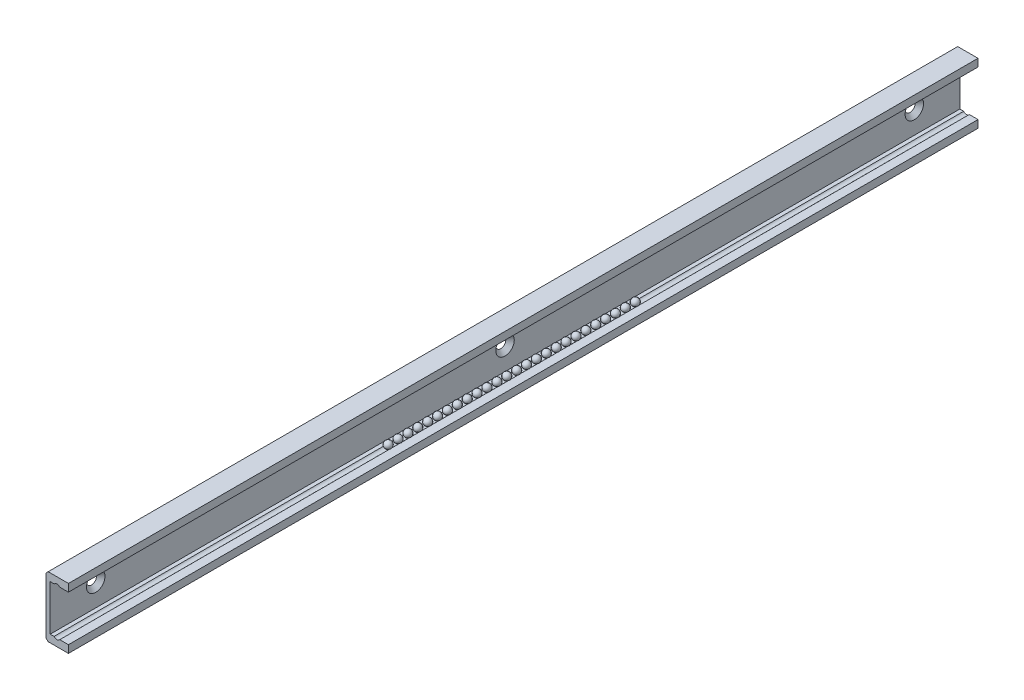
SolidWorks part; units mm, degrees
ref_plane "Front" through (0, 0, 0) normal (0, 0, 1) x (1, 0, 0)
ref_plane "Top" through (0, 0, 0) normal (0, 1, 0) x (1, 0, 0)
ref_plane "Right" through (0, 0, 0) normal (1, 0, 0) x (0, 0, -1)
ref_plane "Plane1" through (0, 0, 0) normal (0, 0, 1) x (1, 0, 0)
sketch "Sketch1" plane through (0, 0, 0) normal (0, 0, 1) x (1, 0, 0)
  line L0 (-7.4, 0.7071) -> (-6.6929, 0)
  line L1 (-6.6929, 0) -> (0, 0)
  line L2 (0, 0) -> (0, 2.5)
  line L3 (0, 2.5) -> (-2.8633, 2.5)
  line L4 (-4.7367, 2.5) -> (-6, 2.5)
  line L5 (-6, 2.5) -> (-6, 17.5)
  line L6 (-6, 17.5) -> (-4.7367, 17.5)
  line L7 (-2.8633, 17.5) -> (0, 17.5)
  line L8 (0, 17.5) -> (0, 20)
  line L9 (0, 20) -> (-6.6929, 20)
  line L10 (-6.6929, 20) -> (-7.4, 19.2929)
  line L11 (-7.4, 19.2929) -> (-7.4, 0.7071)
  arc A0 (-2.8633, 2.5) -> (-4.7367, 2.5) centre (-3.8, 3.25) cw
  arc A1 (-4.7367, 17.5) -> (-2.8633, 17.5) centre (-3.8, 16.75) cw
extrude "Boss-Extrude1" add sketch "Sketch1" along normal blind 300
ref_plane "Plane2" through (0, 0, 15) normal (0, 0, 1) x (1, 0, 0)
sketch "Sketch2" plane through (0, 0, 15) normal (0, 0, 1) x (1, 0, 0)
  line L0 (-7.4, 10) -> (-7.4, 11.65)
  line L1 (-7.4, 11.65) -> (-6, 13.05)
  line L2 (-6, 13.05) -> (-6, 10)
  line L3 (-6, 10) -> (-7.4, 10)
  line L4 (-6, 10) -> (-7.4, 10) construction
revolve "Cut-Revolve1" cut sketch "Sketch2" angle 360 about L4 reverse direction yes
ref_plane "Plane3" through (0, 0, 285) normal (0, 0, 1) x (1, 0, 0)
sketch "Sketch3" plane through (0, 0, 285) normal (0, 0, 1) x (1, 0, 0)
  line L0 (-7.4, 10) -> (-7.4, 11.65)
  line L1 (-7.4, 11.65) -> (-6, 13.05)
  line L2 (-6, 13.05) -> (-6, 10)
  line L3 (-6, 10) -> (-7.4, 10)
  line L4 (-6, 10) -> (-7.4, 10) construction
revolve "Cut-Revolve2" cut sketch "Sketch3" angle 360 about L4 reverse direction yes
ref_plane "Plane4" through (0, 0, 150) normal (0, 0, 1) x (1, 0, 0)
sketch "Sketch4" plane through (0, 0, 150) normal (0, 0, 1) x (1, 0, 0)
  line L0 (-7.4, 10) -> (-7.4, 11.65)
  line L1 (-7.4, 11.65) -> (-6, 13.05)
  line L2 (-6, 13.05) -> (-6, 10)
  line L3 (-6, 10) -> (-7.4, 10)
  line L4 (-6, 10) -> (-7.4, 10) construction
revolve "Cut-Revolve3" cut sketch "Sketch4" angle 360 about L4 reverse direction yes
ref_plane "Plane5" through (0, 3.15, 0) normal (0, 1, 0) x (1, 0, 0)
sketch "Sketch5" plane through (0, 3.15, 0) normal (0, 1, 0) x (1, 0, 0)
  line L0 (-3.8, -110.45) -> (-3.8, -108.05)
  line L1 (-3.8, -110.45) -> (-3.8, -108.05) construction
  arc A0 (-3.8, -108.05) -> (-3.8, -110.45) centre (-3.8, -109.25) cw
revolve "Revolve1" add sketch "Sketch5" angle 360 about L1 reverse direction yes
ref_plane "Plane6" through (0, 3.15, 0) normal (0, 1, 0) x (1, 0, 0)
sketch "Sketch6" plane through (0, 3.15, 0) normal (0, 1, 0) x (1, 0, 0)
  line L0 (-3.8, -113.71) -> (-3.8, -111.31)
  line L1 (-3.8, -113.71) -> (-3.8, -111.31) construction
  arc A0 (-3.8, -111.31) -> (-3.8, -113.71) centre (-3.8, -112.51) cw
revolve "Revolve2" add sketch "Sketch6" angle 360 about L1 reverse direction yes
ref_plane "Plane7" through (0, 3.15, 0) normal (0, 1, 0) x (1, 0, 0)
sketch "Sketch7" plane through (0, 3.15, 0) normal (0, 1, 0) x (1, 0, 0)
  line L0 (-3.8, -116.97) -> (-3.8, -114.57)
  line L1 (-3.8, -116.97) -> (-3.8, -114.57) construction
  arc A0 (-3.8, -114.57) -> (-3.8, -116.97) centre (-3.8, -115.77) cw
revolve "Revolve3" add sketch "Sketch7" angle 360 about L1 reverse direction yes
ref_plane "Plane8" through (0, 3.15, 0) normal (0, 1, 0) x (1, 0, 0)
sketch "Sketch8" plane through (0, 3.15, 0) normal (0, 1, 0) x (1, 0, 0)
  line L0 (-3.8, -120.23) -> (-3.8, -117.83)
  line L1 (-3.8, -120.23) -> (-3.8, -117.83) construction
  arc A0 (-3.8, -117.83) -> (-3.8, -120.23) centre (-3.8, -119.03) cw
revolve "Revolve4" add sketch "Sketch8" angle 360 about L1 reverse direction yes
ref_plane "Plane9" through (0, 3.15, 0) normal (0, 1, 0) x (1, 0, 0)
sketch "Sketch9" plane through (0, 3.15, 0) normal (0, 1, 0) x (1, 0, 0)
  line L0 (-3.8, -123.49) -> (-3.8, -121.09)
  line L1 (-3.8, -123.49) -> (-3.8, -121.09) construction
  arc A0 (-3.8, -121.09) -> (-3.8, -123.49) centre (-3.8, -122.29) cw
revolve "Revolve5" add sketch "Sketch9" angle 360 about L1 reverse direction yes
ref_plane "Plane10" through (0, 3.15, 0) normal (0, 1, 0) x (1, 0, 0)
sketch "Sketch10" plane through (0, 3.15, 0) normal (0, 1, 0) x (1, 0, 0)
  line L0 (-3.8, -126.75) -> (-3.8, -124.35)
  line L1 (-3.8, -126.75) -> (-3.8, -124.35) construction
  arc A0 (-3.8, -124.35) -> (-3.8, -126.75) centre (-3.8, -125.55) cw
revolve "Revolve6" add sketch "Sketch10" angle 360 about L1 reverse direction yes
ref_plane "Plane11" through (0, 3.15, 0) normal (0, 1, 0) x (1, 0, 0)
sketch "Sketch11" plane through (0, 3.15, 0) normal (0, 1, 0) x (1, 0, 0)
  line L0 (-3.8, -130.01) -> (-3.8, -127.61)
  line L1 (-3.8, -130.01) -> (-3.8, -127.61) construction
  arc A0 (-3.8, -127.61) -> (-3.8, -130.01) centre (-3.8, -128.81) cw
revolve "Revolve7" add sketch "Sketch11" angle 360 about L1 reverse direction yes
ref_plane "Plane12" through (0, 3.15, 0) normal (0, 1, 0) x (1, 0, 0)
sketch "Sketch12" plane through (0, 3.15, 0) normal (0, 1, 0) x (1, 0, 0)
  line L0 (-3.8, -133.27) -> (-3.8, -130.87)
  line L1 (-3.8, -133.27) -> (-3.8, -130.87) construction
  arc A0 (-3.8, -130.87) -> (-3.8, -133.27) centre (-3.8, -132.07) cw
revolve "Revolve8" add sketch "Sketch12" angle 360 about L1 reverse direction yes
ref_plane "Plane13" through (0, 3.15, 0) normal (0, 1, 0) x (1, 0, 0)
sketch "Sketch13" plane through (0, 3.15, 0) normal (0, 1, 0) x (1, 0, 0)
  line L0 (-3.8, -136.53) -> (-3.8, -134.13)
  line L1 (-3.8, -136.53) -> (-3.8, -134.13) construction
  arc A0 (-3.8, -134.13) -> (-3.8, -136.53) centre (-3.8, -135.33) cw
revolve "Revolve9" add sketch "Sketch13" angle 360 about L1 reverse direction yes
ref_plane "Plane14" through (0, 3.15, 0) normal (0, 1, 0) x (1, 0, 0)
sketch "Sketch14" plane through (0, 3.15, 0) normal (0, 1, 0) x (1, 0, 0)
  line L0 (-3.8, -139.79) -> (-3.8, -137.39)
  line L1 (-3.8, -139.79) -> (-3.8, -137.39) construction
  arc A0 (-3.8, -137.39) -> (-3.8, -139.79) centre (-3.8, -138.59) cw
revolve "Revolve10" add sketch "Sketch14" angle 360 about L1 reverse direction yes
ref_plane "Plane15" through (0, 3.15, 0) normal (0, 1, 0) x (1, 0, 0)
sketch "Sketch15" plane through (0, 3.15, 0) normal (0, 1, 0) x (1, 0, 0)
  line L0 (-3.8, -143.05) -> (-3.8, -140.65)
  line L1 (-3.8, -143.05) -> (-3.8, -140.65) construction
  arc A0 (-3.8, -140.65) -> (-3.8, -143.05) centre (-3.8, -141.85) cw
revolve "Revolve11" add sketch "Sketch15" angle 360 about L1 reverse direction yes
ref_plane "Plane16" through (0, 3.15, 0) normal (0, 1, 0) x (1, 0, 0)
sketch "Sketch16" plane through (0, 3.15, 0) normal (0, 1, 0) x (1, 0, 0)
  line L0 (-3.8, -146.31) -> (-3.8, -143.91)
  line L1 (-3.8, -146.31) -> (-3.8, -143.91) construction
  arc A0 (-3.8, -143.91) -> (-3.8, -146.31) centre (-3.8, -145.11) cw
revolve "Revolve12" add sketch "Sketch16" angle 360 about L1 reverse direction yes
ref_plane "Plane17" through (0, 3.15, 0) normal (0, 1, 0) x (1, 0, 0)
sketch "Sketch17" plane through (0, 3.15, 0) normal (0, 1, 0) x (1, 0, 0)
  line L0 (-3.8, -149.57) -> (-3.8, -147.17)
  line L1 (-3.8, -149.57) -> (-3.8, -147.17) construction
  arc A0 (-3.8, -147.17) -> (-3.8, -149.57) centre (-3.8, -148.37) cw
revolve "Revolve13" add sketch "Sketch17" angle 360 about L1 reverse direction yes
ref_plane "Plane18" through (0, 3.15, 0) normal (0, 1, 0) x (1, 0, 0)
sketch "Sketch18" plane through (0, 3.15, 0) normal (0, 1, 0) x (1, 0, 0)
  line L0 (-3.8, -152.83) -> (-3.8, -150.43)
  line L1 (-3.8, -152.83) -> (-3.8, -150.43) construction
  arc A0 (-3.8, -150.43) -> (-3.8, -152.83) centre (-3.8, -151.63) cw
revolve "Revolve14" add sketch "Sketch18" angle 360 about L1 reverse direction yes
ref_plane "Plane19" through (0, 3.15, 0) normal (0, 1, 0) x (1, 0, 0)
sketch "Sketch19" plane through (0, 3.15, 0) normal (0, 1, 0) x (1, 0, 0)
  line L0 (-3.8, -156.09) -> (-3.8, -153.69)
  line L1 (-3.8, -156.09) -> (-3.8, -153.69) construction
  arc A0 (-3.8, -153.69) -> (-3.8, -156.09) centre (-3.8, -154.89) cw
revolve "Revolve15" add sketch "Sketch19" angle 360 about L1 reverse direction yes
ref_plane "Plane20" through (0, 3.15, 0) normal (0, 1, 0) x (1, 0, 0)
sketch "Sketch20" plane through (0, 3.15, 0) normal (0, 1, 0) x (1, 0, 0)
  line L0 (-3.8, -159.35) -> (-3.8, -156.95)
  line L1 (-3.8, -159.35) -> (-3.8, -156.95) construction
  arc A0 (-3.8, -156.95) -> (-3.8, -159.35) centre (-3.8, -158.15) cw
revolve "Revolve16" add sketch "Sketch20" angle 360 about L1 reverse direction yes
ref_plane "Plane21" through (0, 3.15, 0) normal (0, 1, 0) x (1, 0, 0)
sketch "Sketch21" plane through (0, 3.15, 0) normal (0, 1, 0) x (1, 0, 0)
  line L0 (-3.8, -162.61) -> (-3.8, -160.21)
  line L1 (-3.8, -162.61) -> (-3.8, -160.21) construction
  arc A0 (-3.8, -160.21) -> (-3.8, -162.61) centre (-3.8, -161.41) cw
revolve "Revolve17" add sketch "Sketch21" angle 360 about L1 reverse direction yes
ref_plane "Plane22" through (0, 3.15, 0) normal (0, 1, 0) x (1, 0, 0)
sketch "Sketch22" plane through (0, 3.15, 0) normal (0, 1, 0) x (1, 0, 0)
  line L0 (-3.8, -165.87) -> (-3.8, -163.47)
  line L1 (-3.8, -165.87) -> (-3.8, -163.47) construction
  arc A0 (-3.8, -163.47) -> (-3.8, -165.87) centre (-3.8, -164.67) cw
revolve "Revolve18" add sketch "Sketch22" angle 360 about L1 reverse direction yes
ref_plane "Plane23" through (0, 3.15, 0) normal (0, 1, 0) x (1, 0, 0)
sketch "Sketch23" plane through (0, 3.15, 0) normal (0, 1, 0) x (1, 0, 0)
  line L0 (-3.8, -169.13) -> (-3.8, -166.73)
  line L1 (-3.8, -169.13) -> (-3.8, -166.73) construction
  arc A0 (-3.8, -166.73) -> (-3.8, -169.13) centre (-3.8, -167.93) cw
revolve "Revolve19" add sketch "Sketch23" angle 360 about L1 reverse direction yes
ref_plane "Plane24" through (0, 3.15, 0) normal (0, 1, 0) x (1, 0, 0)
sketch "Sketch24" plane through (0, 3.15, 0) normal (0, 1, 0) x (1, 0, 0)
  line L0 (-3.8, -172.39) -> (-3.8, -169.99)
  line L1 (-3.8, -172.39) -> (-3.8, -169.99) construction
  arc A0 (-3.8, -169.99) -> (-3.8, -172.39) centre (-3.8, -171.19) cw
revolve "Revolve20" add sketch "Sketch24" angle 360 about L1 reverse direction yes
ref_plane "Plane25" through (0, 3.15, 0) normal (0, 1, 0) x (1, 0, 0)
sketch "Sketch25" plane through (0, 3.15, 0) normal (0, 1, 0) x (1, 0, 0)
  line L0 (-3.8, -175.65) -> (-3.8, -173.25)
  line L1 (-3.8, -175.65) -> (-3.8, -173.25) construction
  arc A0 (-3.8, -173.25) -> (-3.8, -175.65) centre (-3.8, -174.45) cw
revolve "Revolve21" add sketch "Sketch25" angle 360 about L1 reverse direction yes
ref_plane "Plane26" through (0, 3.15, 0) normal (0, 1, 0) x (1, 0, 0)
sketch "Sketch26" plane through (0, 3.15, 0) normal (0, 1, 0) x (1, 0, 0)
  line L0 (-3.8, -178.91) -> (-3.8, -176.51)
  line L1 (-3.8, -178.91) -> (-3.8, -176.51) construction
  arc A0 (-3.8, -176.51) -> (-3.8, -178.91) centre (-3.8, -177.71) cw
revolve "Revolve22" add sketch "Sketch26" angle 360 about L1 reverse direction yes
ref_plane "Plane27" through (0, 3.15, 0) normal (0, 1, 0) x (1, 0, 0)
sketch "Sketch27" plane through (0, 3.15, 0) normal (0, 1, 0) x (1, 0, 0)
  line L0 (-3.8, -182.17) -> (-3.8, -179.77)
  line L1 (-3.8, -182.17) -> (-3.8, -179.77) construction
  arc A0 (-3.8, -179.77) -> (-3.8, -182.17) centre (-3.8, -180.97) cw
revolve "Revolve23" add sketch "Sketch27" angle 360 about L1 reverse direction yes
ref_plane "Plane28" through (0, 3.15, 0) normal (0, 1, 0) x (1, 0, 0)
sketch "Sketch28" plane through (0, 3.15, 0) normal (0, 1, 0) x (1, 0, 0)
  line L0 (-3.8, -185.43) -> (-3.8, -183.03)
  line L1 (-3.8, -185.43) -> (-3.8, -183.03) construction
  arc A0 (-3.8, -183.03) -> (-3.8, -185.43) centre (-3.8, -184.23) cw
revolve "Revolve24" add sketch "Sketch28" angle 360 about L1 reverse direction yes
ref_plane "Plane29" through (0, 3.15, 0) normal (0, 1, 0) x (1, 0, 0)
sketch "Sketch29" plane through (0, 3.15, 0) normal (0, 1, 0) x (1, 0, 0)
  line L0 (-3.8, -188.69) -> (-3.8, -186.29)
  line L1 (-3.8, -188.69) -> (-3.8, -186.29) construction
  arc A0 (-3.8, -186.29) -> (-3.8, -188.69) centre (-3.8, -187.49) cw
revolve "Revolve25" add sketch "Sketch29" angle 360 about L1 reverse direction yes
ref_plane "Plane30" through (0, 3.15, 0) normal (0, 1, 0) x (1, 0, 0)
sketch "Sketch30" plane through (0, 3.15, 0) normal (0, 1, 0) x (1, 0, 0)
  line L0 (-3.8, -191.95) -> (-3.8, -189.55)
  line L1 (-3.8, -191.95) -> (-3.8, -189.55) construction
  arc A0 (-3.8, -189.55) -> (-3.8, -191.95) centre (-3.8, -190.75) cw
revolve "Revolve26" add sketch "Sketch30" angle 360 about L1 reverse direction yes
ref_plane "Plane31" through (0, 16.85, 0) normal (0, 1, 0) x (1, 0, 0)
sketch "Sketch31" plane through (0, 16.85, 0) normal (0, 1, 0) x (1, 0, 0)
  line L0 (-3.8, -110.45) -> (-3.8, -108.05)
  line L1 (-3.8, -110.45) -> (-3.8, -108.05) construction
  arc A0 (-3.8, -108.05) -> (-3.8, -110.45) centre (-3.8, -109.25) cw
revolve "Revolve27" add sketch "Sketch31" angle 360 about L1 reverse direction yes
ref_plane "Plane32" through (0, 16.85, 0) normal (0, 1, 0) x (1, 0, 0)
sketch "Sketch32" plane through (0, 16.85, 0) normal (0, 1, 0) x (1, 0, 0)
  line L0 (-3.8, -113.71) -> (-3.8, -111.31)
  line L1 (-3.8, -113.71) -> (-3.8, -111.31) construction
  arc A0 (-3.8, -111.31) -> (-3.8, -113.71) centre (-3.8, -112.51) cw
revolve "Revolve28" add sketch "Sketch32" angle 360 about L1 reverse direction yes
ref_plane "Plane33" through (0, 16.85, 0) normal (0, 1, 0) x (1, 0, 0)
sketch "Sketch33" plane through (0, 16.85, 0) normal (0, 1, 0) x (1, 0, 0)
  line L0 (-3.8, -116.97) -> (-3.8, -114.57)
  line L1 (-3.8, -116.97) -> (-3.8, -114.57) construction
  arc A0 (-3.8, -114.57) -> (-3.8, -116.97) centre (-3.8, -115.77) cw
revolve "Revolve29" add sketch "Sketch33" angle 360 about L1 reverse direction yes
ref_plane "Plane34" through (0, 16.85, 0) normal (0, 1, 0) x (1, 0, 0)
sketch "Sketch34" plane through (0, 16.85, 0) normal (0, 1, 0) x (1, 0, 0)
  line L0 (-3.8, -120.23) -> (-3.8, -117.83)
  line L1 (-3.8, -120.23) -> (-3.8, -117.83) construction
  arc A0 (-3.8, -117.83) -> (-3.8, -120.23) centre (-3.8, -119.03) cw
revolve "Revolve30" add sketch "Sketch34" angle 360 about L1 reverse direction yes
ref_plane "Plane35" through (0, 16.85, 0) normal (0, 1, 0) x (1, 0, 0)
sketch "Sketch35" plane through (0, 16.85, 0) normal (0, 1, 0) x (1, 0, 0)
  line L0 (-3.8, -123.49) -> (-3.8, -121.09)
  line L1 (-3.8, -123.49) -> (-3.8, -121.09) construction
  arc A0 (-3.8, -121.09) -> (-3.8, -123.49) centre (-3.8, -122.29) cw
revolve "Revolve31" add sketch "Sketch35" angle 360 about L1 reverse direction yes
ref_plane "Plane36" through (0, 16.85, 0) normal (0, 1, 0) x (1, 0, 0)
sketch "Sketch36" plane through (0, 16.85, 0) normal (0, 1, 0) x (1, 0, 0)
  line L0 (-3.8, -126.75) -> (-3.8, -124.35)
  line L1 (-3.8, -126.75) -> (-3.8, -124.35) construction
  arc A0 (-3.8, -124.35) -> (-3.8, -126.75) centre (-3.8, -125.55) cw
revolve "Revolve32" add sketch "Sketch36" angle 360 about L1 reverse direction yes
ref_plane "Plane37" through (0, 16.85, 0) normal (0, 1, 0) x (1, 0, 0)
sketch "Sketch37" plane through (0, 16.85, 0) normal (0, 1, 0) x (1, 0, 0)
  line L0 (-3.8, -130.01) -> (-3.8, -127.61)
  line L1 (-3.8, -130.01) -> (-3.8, -127.61) construction
  arc A0 (-3.8, -127.61) -> (-3.8, -130.01) centre (-3.8, -128.81) cw
revolve "Revolve33" add sketch "Sketch37" angle 360 about L1 reverse direction yes
ref_plane "Plane38" through (0, 16.85, 0) normal (0, 1, 0) x (1, 0, 0)
sketch "Sketch38" plane through (0, 16.85, 0) normal (0, 1, 0) x (1, 0, 0)
  line L0 (-3.8, -133.27) -> (-3.8, -130.87)
  line L1 (-3.8, -133.27) -> (-3.8, -130.87) construction
  arc A0 (-3.8, -130.87) -> (-3.8, -133.27) centre (-3.8, -132.07) cw
revolve "Revolve34" add sketch "Sketch38" angle 360 about L1 reverse direction yes
ref_plane "Plane39" through (0, 16.85, 0) normal (0, 1, 0) x (1, 0, 0)
sketch "Sketch39" plane through (0, 16.85, 0) normal (0, 1, 0) x (1, 0, 0)
  line L0 (-3.8, -136.53) -> (-3.8, -134.13)
  line L1 (-3.8, -136.53) -> (-3.8, -134.13) construction
  arc A0 (-3.8, -134.13) -> (-3.8, -136.53) centre (-3.8, -135.33) cw
revolve "Revolve35" add sketch "Sketch39" angle 360 about L1 reverse direction yes
ref_plane "Plane40" through (0, 16.85, 0) normal (0, 1, 0) x (1, 0, 0)
sketch "Sketch40" plane through (0, 16.85, 0) normal (0, 1, 0) x (1, 0, 0)
  line L0 (-3.8, -139.79) -> (-3.8, -137.39)
  line L1 (-3.8, -139.79) -> (-3.8, -137.39) construction
  arc A0 (-3.8, -137.39) -> (-3.8, -139.79) centre (-3.8, -138.59) cw
revolve "Revolve36" add sketch "Sketch40" angle 360 about L1 reverse direction yes
ref_plane "Plane41" through (0, 16.85, 0) normal (0, 1, 0) x (1, 0, 0)
sketch "Sketch41" plane through (0, 16.85, 0) normal (0, 1, 0) x (1, 0, 0)
  line L0 (-3.8, -143.05) -> (-3.8, -140.65)
  line L1 (-3.8, -143.05) -> (-3.8, -140.65) construction
  arc A0 (-3.8, -140.65) -> (-3.8, -143.05) centre (-3.8, -141.85) cw
revolve "Revolve37" add sketch "Sketch41" angle 360 about L1 reverse direction yes
ref_plane "Plane42" through (0, 16.85, 0) normal (0, 1, 0) x (1, 0, 0)
sketch "Sketch42" plane through (0, 16.85, 0) normal (0, 1, 0) x (1, 0, 0)
  line L0 (-3.8, -146.31) -> (-3.8, -143.91)
  line L1 (-3.8, -146.31) -> (-3.8, -143.91) construction
  arc A0 (-3.8, -143.91) -> (-3.8, -146.31) centre (-3.8, -145.11) cw
revolve "Revolve38" add sketch "Sketch42" angle 360 about L1 reverse direction yes
ref_plane "Plane43" through (0, 16.85, 0) normal (0, 1, 0) x (1, 0, 0)
sketch "Sketch43" plane through (0, 16.85, 0) normal (0, 1, 0) x (1, 0, 0)
  line L0 (-3.8, -149.57) -> (-3.8, -147.17)
  line L1 (-3.8, -149.57) -> (-3.8, -147.17) construction
  arc A0 (-3.8, -147.17) -> (-3.8, -149.57) centre (-3.8, -148.37) cw
revolve "Revolve39" add sketch "Sketch43" angle 360 about L1 reverse direction yes
ref_plane "Plane44" through (0, 16.85, 0) normal (0, 1, 0) x (1, 0, 0)
sketch "Sketch44" plane through (0, 16.85, 0) normal (0, 1, 0) x (1, 0, 0)
  line L0 (-3.8, -152.83) -> (-3.8, -150.43)
  line L1 (-3.8, -152.83) -> (-3.8, -150.43) construction
  arc A0 (-3.8, -150.43) -> (-3.8, -152.83) centre (-3.8, -151.63) cw
revolve "Revolve40" add sketch "Sketch44" angle 360 about L1 reverse direction yes
ref_plane "Plane45" through (0, 16.85, 0) normal (0, 1, 0) x (1, 0, 0)
sketch "Sketch45" plane through (0, 16.85, 0) normal (0, 1, 0) x (1, 0, 0)
  line L0 (-3.8, -156.09) -> (-3.8, -153.69)
  line L1 (-3.8, -156.09) -> (-3.8, -153.69) construction
  arc A0 (-3.8, -153.69) -> (-3.8, -156.09) centre (-3.8, -154.89) cw
revolve "Revolve41" add sketch "Sketch45" angle 360 about L1 reverse direction yes
ref_plane "Plane46" through (0, 16.85, 0) normal (0, 1, 0) x (1, 0, 0)
sketch "Sketch46" plane through (0, 16.85, 0) normal (0, 1, 0) x (1, 0, 0)
  line L0 (-3.8, -159.35) -> (-3.8, -156.95)
  line L1 (-3.8, -159.35) -> (-3.8, -156.95) construction
  arc A0 (-3.8, -156.95) -> (-3.8, -159.35) centre (-3.8, -158.15) cw
revolve "Revolve42" add sketch "Sketch46" angle 360 about L1 reverse direction yes
ref_plane "Plane47" through (0, 16.85, 0) normal (0, 1, 0) x (1, 0, 0)
sketch "Sketch47" plane through (0, 16.85, 0) normal (0, 1, 0) x (1, 0, 0)
  line L0 (-3.8, -162.61) -> (-3.8, -160.21)
  line L1 (-3.8, -162.61) -> (-3.8, -160.21) construction
  arc A0 (-3.8, -160.21) -> (-3.8, -162.61) centre (-3.8, -161.41) cw
revolve "Revolve43" add sketch "Sketch47" angle 360 about L1 reverse direction yes
ref_plane "Plane48" through (0, 16.85, 0) normal (0, 1, 0) x (1, 0, 0)
sketch "Sketch48" plane through (0, 16.85, 0) normal (0, 1, 0) x (1, 0, 0)
  line L0 (-3.8, -165.87) -> (-3.8, -163.47)
  line L1 (-3.8, -165.87) -> (-3.8, -163.47) construction
  arc A0 (-3.8, -163.47) -> (-3.8, -165.87) centre (-3.8, -164.67) cw
revolve "Revolve44" add sketch "Sketch48" angle 360 about L1 reverse direction yes
ref_plane "Plane49" through (0, 16.85, 0) normal (0, 1, 0) x (1, 0, 0)
sketch "Sketch49" plane through (0, 16.85, 0) normal (0, 1, 0) x (1, 0, 0)
  line L0 (-3.8, -169.13) -> (-3.8, -166.73)
  line L1 (-3.8, -169.13) -> (-3.8, -166.73) construction
  arc A0 (-3.8, -166.73) -> (-3.8, -169.13) centre (-3.8, -167.93) cw
revolve "Revolve45" add sketch "Sketch49" angle 360 about L1 reverse direction yes
ref_plane "Plane50" through (0, 16.85, 0) normal (0, 1, 0) x (1, 0, 0)
sketch "Sketch50" plane through (0, 16.85, 0) normal (0, 1, 0) x (1, 0, 0)
  line L0 (-3.8, -172.39) -> (-3.8, -169.99)
  line L1 (-3.8, -172.39) -> (-3.8, -169.99) construction
  arc A0 (-3.8, -169.99) -> (-3.8, -172.39) centre (-3.8, -171.19) cw
revolve "Revolve46" add sketch "Sketch50" angle 360 about L1 reverse direction yes
ref_plane "Plane51" through (0, 16.85, 0) normal (0, 1, 0) x (1, 0, 0)
sketch "Sketch51" plane through (0, 16.85, 0) normal (0, 1, 0) x (1, 0, 0)
  line L0 (-3.8, -175.65) -> (-3.8, -173.25)
  line L1 (-3.8, -175.65) -> (-3.8, -173.25) construction
  arc A0 (-3.8, -173.25) -> (-3.8, -175.65) centre (-3.8, -174.45) cw
revolve "Revolve47" add sketch "Sketch51" angle 360 about L1 reverse direction yes
ref_plane "Plane52" through (0, 16.85, 0) normal (0, 1, 0) x (1, 0, 0)
sketch "Sketch52" plane through (0, 16.85, 0) normal (0, 1, 0) x (1, 0, 0)
  line L0 (-3.8, -178.91) -> (-3.8, -176.51)
  line L1 (-3.8, -178.91) -> (-3.8, -176.51) construction
  arc A0 (-3.8, -176.51) -> (-3.8, -178.91) centre (-3.8, -177.71) cw
revolve "Revolve48" add sketch "Sketch52" angle 360 about L1 reverse direction yes
ref_plane "Plane53" through (0, 16.85, 0) normal (0, 1, 0) x (1, 0, 0)
sketch "Sketch53" plane through (0, 16.85, 0) normal (0, 1, 0) x (1, 0, 0)
  line L0 (-3.8, -182.17) -> (-3.8, -179.77)
  line L1 (-3.8, -182.17) -> (-3.8, -179.77) construction
  arc A0 (-3.8, -179.77) -> (-3.8, -182.17) centre (-3.8, -180.97) cw
revolve "Revolve49" add sketch "Sketch53" angle 360 about L1 reverse direction yes
ref_plane "Plane54" through (0, 16.85, 0) normal (0, 1, 0) x (1, 0, 0)
sketch "Sketch54" plane through (0, 16.85, 0) normal (0, 1, 0) x (1, 0, 0)
  line L0 (-3.8, -185.43) -> (-3.8, -183.03)
  line L1 (-3.8, -185.43) -> (-3.8, -183.03) construction
  arc A0 (-3.8, -183.03) -> (-3.8, -185.43) centre (-3.8, -184.23) cw
revolve "Revolve50" add sketch "Sketch54" angle 360 about L1 reverse direction yes
ref_plane "Plane55" through (0, 16.85, 0) normal (0, 1, 0) x (1, 0, 0)
sketch "Sketch55" plane through (0, 16.85, 0) normal (0, 1, 0) x (1, 0, 0)
  line L0 (-3.8, -188.69) -> (-3.8, -186.29)
  line L1 (-3.8, -188.69) -> (-3.8, -186.29) construction
  arc A0 (-3.8, -186.29) -> (-3.8, -188.69) centre (-3.8, -187.49) cw
revolve "Revolve51" add sketch "Sketch55" angle 360 about L1 reverse direction yes
ref_plane "Plane56" through (0, 16.85, 0) normal (0, 1, 0) x (1, 0, 0)
sketch "Sketch56" plane through (0, 16.85, 0) normal (0, 1, 0) x (1, 0, 0)
  line L0 (-3.8, -191.95) -> (-3.8, -189.55)
  line L1 (-3.8, -191.95) -> (-3.8, -189.55) construction
  arc A0 (-3.8, -189.55) -> (-3.8, -191.95) centre (-3.8, -190.75) cw
revolve "Revolve52" add sketch "Sketch56" angle 360 about L1 reverse direction yes
